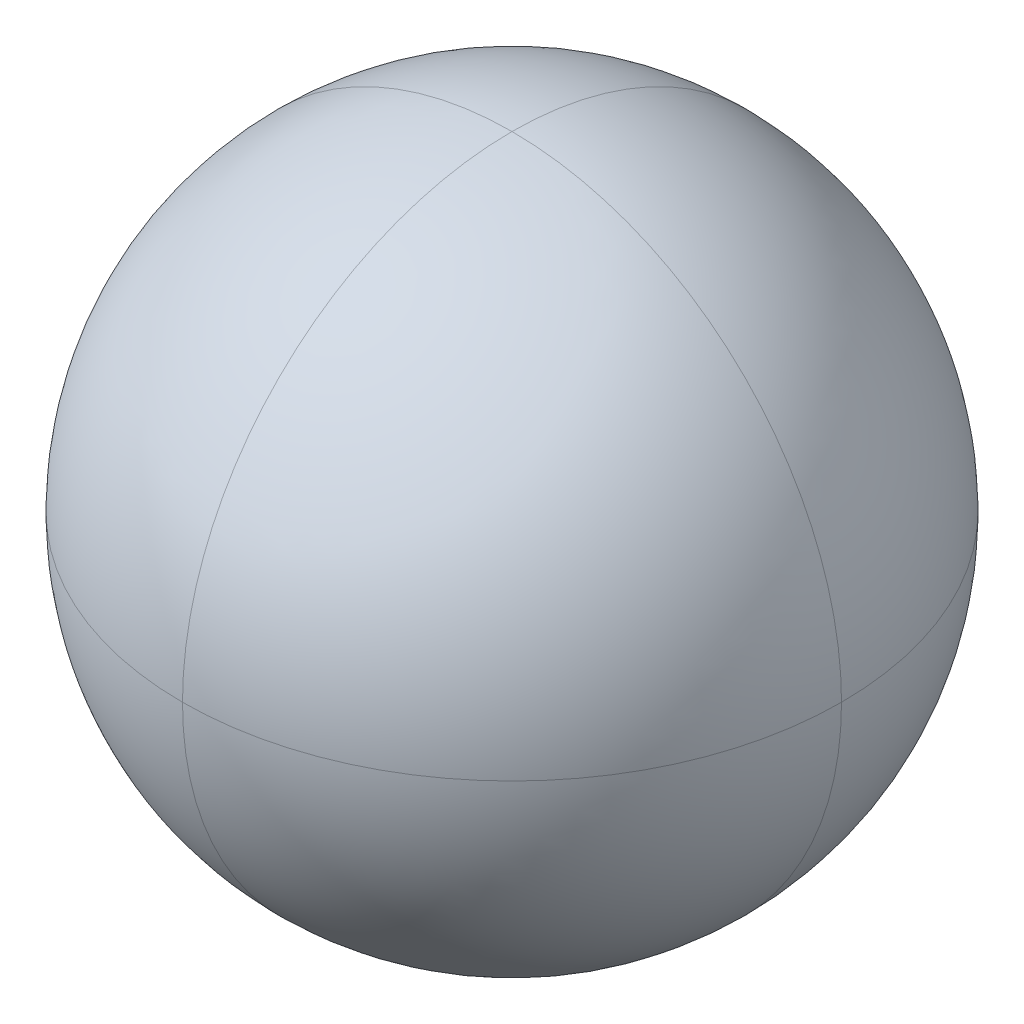
SolidWorks part; units mm, degrees
ref_plane "Front Plane" through (0, 0, 0) normal (0, 0, 1) x (1, 0, 0)
ref_plane "Top Plane" through (0, 0, 0) normal (0, 1, 0) x (1, 0, 0)
ref_plane "Right Plane" through (0, 0, 0) normal (1, 0, 0) x (0, 0, -1)
sketch "Sketch1" plane through (0, 0, 0) normal (0, 0, 1) x (1, 0, 0)
  line L1 (0, 0) -> (254, 0)
  line L2 (0, 0) -> (0, 254)
  line L3 (0, 254) -> (254, 254)
  line L4 (254, 0) -> (254, 254)
  dimension "D1" = 254
  dimension "D2" = 254
extrude "Boss-Extrude1" add sketch "Sketch1" along normal blind 254
fillet "Fillet1" radius 127 12 edges at (254, 127, 254) (127, 254, 254) (0, 127, 254) (127, 254, 0) (254, 127, 0) (127, 0, 0) (0, 127, 0) (127, 0, 254) (0, 254, 127) (254, 254, 127) (254, 0, 127) (0, 0, 127)
